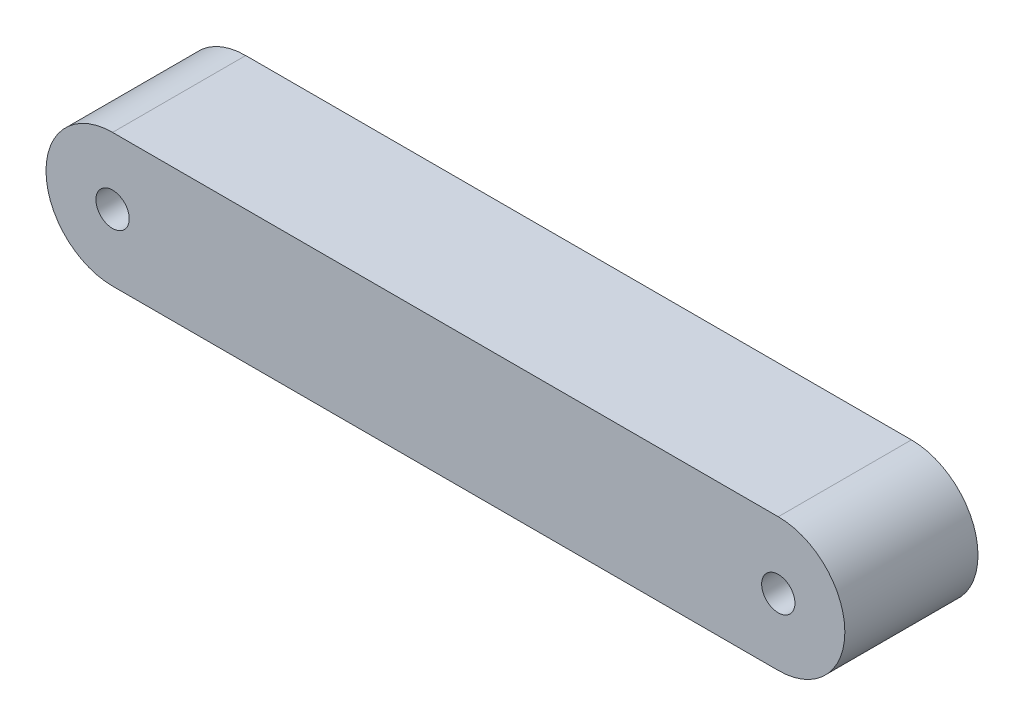
SolidWorks part; units mm, degrees
ref_plane "前视基准面" through (0, 0, 0) normal (0, 0, 1) x (1, 0, 0)
ref_plane "上视基准面" through (0, 0, 0) normal (0, 1, 0) x (1, 0, 0)
ref_plane "右视基准面" through (0, 0, 0) normal (1, 0, 0) x (0, 0, -1)
other "Configuration Table"
sketch "草图1" plane through (0, 0, 0) normal (0, 0, 1) x (1, 0, 0)
  line L0 (-1000, 0) -> (0, 0) construction
  line L2 (0, 2) -> (20, 2)
  line L3 (0, -2) -> (20, -2)
  line L4 (22, 0) -> (49000, 0) construction
  arc A0 (0, 2) -> (0, -2) centre (0, 0) ccw
  arc A1 (20, -2) -> (20, 2) centre (20, 0) ccw
  circle A2 centre (0, 0) radius 0.5
  circle A3 centre (20, 0) radius 0.5
  dimension "D1" = 4
  dimension "D3" = 4
  dimension "D4" = 1
  dimension "D5" = 1
  dimension "D2" = 20
extrude "凸台-拉伸1" add sketch "草图1" along normal blind 4
